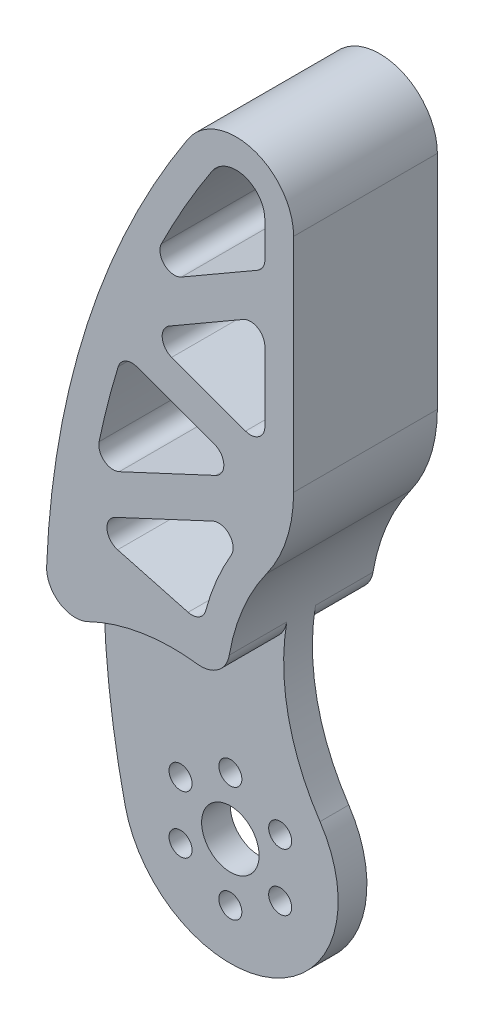
SolidWorks part; units mm, degrees
ref_plane "前视基准面" through (0, 0, 0) normal (0, 0, 1) x (1, 0, 0)
ref_plane "上视基准面" through (0, 0, 0) normal (0, 1, 0) x (1, 0, 0)
ref_plane "右视基准面" through (0, 0, 0) normal (1, 0, 0) x (0, 0, -1)
sketch "草图1" plane through (0, 0, 0) normal (0, 0, 1) x (1, 0, 0)
  circle A0 centre (0, 0) radius 4
  circle A1 centre (0, 0) radius 8 construction
  circle A2 centre (0, 0) radius 15
  circle A3 centre (0, 8) radius 1.6
  circle A4 centre (6.9282, 4) radius 1.6
  circle A5 centre (6.9282, -4) radius 1.6
  circle A6 centre (0, -8) radius 1.6
  circle A7 centre (-6.9282, -4) radius 1.6
  circle A8 centre (-6.9282, 4) radius 1.6
  point P16 (0, 0)
  dimension "D1" = 3.2
  dimension "D2" = 16
  dimension "D3" = 8
  dimension "D4" = 30
  dimension "D5" = 6
extrude "凸台-拉伸1" add sketch "草图1" along normal blind 4
sketch "草图2" plane through (0, 0, 4) normal (0, 0, 1) x (1, 0, 0)
  line L1 (16.8, 85) -> (16.8, 54.1598)
  arc A0 (-14.622, -3.3462) -> (2.1176, 89.3983) centre (102.354, 23.4236) cw
  circle A1 centre (0, 0) radius 15 construction
  arc A2 (12.4722, 8.3333) -> (13.0466, 42.4959) centre (37.4166, 25) cw
  arc A3 (12.4722, 8.3333) -> (-14.622, -3.3462) centre (0, 0) ccw
  arc A4 (2.1176, 89.3983) -> (16.8, 85) centre (8.8, 85) cw
  arc A5 (16.8, 54.1598) -> (13.0466, 42.4959) centre (-3.2, 54.1598) cw
  dimension "D1" = 8
  dimension "D4" = 30
  dimension "D5" = 120
  dimension "D6" = 20
  dimension "D2" = 85
  dimension "D3" = 16.8
  dimension "D7" = 25
extrude "凸台-拉伸3" add sketch "草图2" against normal up to surface (4 mm away) up to face at (15, 0, 0)
sketch "草图3" plane through (0, 0, 4) normal (0, 0, 1) x (1, 0, 0)
  line L1 (16.8, 54.1598) -> (16.8, 85)
  line L2 (16.8, 54.1598) -> (16.8, 85)
  arc A0 (-11.8108, 24.2797) -> (3.4027, 26.7847) centre (0, 0) cw
  arc A1 (2.1176, 89.3983) -> (-14.622, -3.3462) centre (102.354, 23.4236) ccw construction
  arc A2 (13.0466, 42.4959) -> (12.4722, 8.3333) centre (37.4166, 25) ccw construction
  circle A3 centre (0, 0) radius 4 construction
  arc A4 (3.4027, 26.7847) -> (7.8491, 30.076) centre (3.9068, 30.7528) ccw
  arc A5 (-11.8108, 24.2797) -> (-17.5576, 28.0303) centre (-13.5605, 27.8767) cw
  arc A9 (-14.622, -3.3462) -> (12.4722, 8.3333) centre (0, 0) ccw
  arc A10 (13.0466, 42.4959) -> (12.4722, 8.3333) centre (37.4166, 25) ccw
  arc A11 (13.0466, 42.4959) -> (16.8, 54.1598) centre (-3.2, 54.1598) ccw
  arc A12 (16.8, 85) -> (2.1176, 89.3983) centre (8.8, 85) ccw
  arc A13 (2.1176, 89.3983) -> (-14.622, -3.3462) centre (102.354, 23.4236) ccw
  arc A15 (13.0466, 42.4959) -> (7.8491, 30.076) centre (37.4166, 25) ccw
  arc A16 (13.0466, 42.4959) -> (16.8, 54.1598) centre (-3.2, 54.1598) ccw
  arc A17 (16.8, 85) -> (2.1176, 89.3983) centre (8.8, 85) ccw
  arc A18 (2.1176, 89.3983) -> (-17.5576, 28.0303) centre (102.354, 23.4236) ccw
  point P17 (7.4318, 25.957)
  point P27 (-17.6096, 20.4671)
  dimension "D1" = 27
  dimension "D3" = 4
  dimension "D2" = 0
extrude "凸台-拉伸4" add sketch "草图3" along normal blind 8 and the other way blind 12
sketch "草图5" plane through (0, 0, -8) normal (0, 0, -1) x (-1, 0, 0)
  line L0 (-12.8, 69.7624) -> (-12.8, 60.0828)
  line L1 (-11.8, 78.4226) -> (-1.2064, 72.3064)
  line L2 (-12.8, 85) -> (-12.8, 54.1598)
  line L3 (-12.8, 85) -> (-12.8, 80.1547)
  line L4 (-10.116, 58.2034) -> (0.167, 61.9461)
  line L5 (0.483, 65.5576) -> (-9.8, 71.4944)
  line L6 (5.0101, 58.3879) -> (-5.777, 54.4618)
  line L7 (-5.9382, 50.7698) -> (7.4531, 44.5253)
  line L8 (-2.1233, 32.3771) -> (7.682, 35.0045)
  line L9 (8.0096, 38.7489) -> (-5.5439, 45.069)
  arc A0 (7.6065, 57.0941) -> (10.2568, 46.7435) centre (-102.354, 23.4236) cw
  arc A1 (17.5576, 28.0303) -> (-2.1176, 89.3983) centre (-102.354, 23.4236) ccw construction
  arc A2 (-8.1128, 42.2421) -> (-4.5729, 33.7918) centre (-37.4166, 25) cw
  arc A3 (-7.8491, 30.076) -> (-13.0466, 42.4959) centre (-37.4166, 25) ccw construction
  arc A4 (7.682, 35.0045) -> (8.0096, 38.7489) centre (7.1643, 36.9363) ccw
  arc A5 (-5.777, 54.4618) -> (-5.9382, 50.7698) centre (-5.093, 52.5824) ccw
  arc A6 (-4.5729, 33.7918) -> (-2.1233, 32.3771) centre (-2.641, 34.309) ccw
  arc A7 (10.2568, 46.7435) -> (7.4531, 44.5253) centre (8.2983, 46.3379) cw
  arc A8 (-8.1128, 42.2421) -> (-5.5439, 45.069) centre (-6.3891, 43.2564) cw
  arc A9 (0.167, 61.9461) -> (0.483, 65.5576) centre (-0.517, 63.8255) ccw
  arc A10 (7.6065, 57.0941) -> (5.0101, 58.3879) centre (5.6941, 56.5086) ccw
  arc A11 (-12.8, 60.0828) -> (-10.116, 58.2034) centre (-10.8, 60.0828) ccw
  arc A12 (-12.8, 69.7624) -> (-9.8, 71.4944) centre (-10.8, 69.7624) cw
  arc A13 (-1.2064, 72.3064) -> (1.5857, 74.9264) centre (-0.2064, 74.0385) ccw
  arc A14 (13.5605, 27.8767) -> (-3.9068, 30.7528) centre (0, 0) ccw
  arc A15 (13.5605, 27.8767) -> (-5.4588, 87.1992) centre (-102.354, 23.4236) ccw
  arc A16 (-5.4588, 87.1992) -> (-12.8, 85) centre (-8.8, 85) ccw
  arc A17 (-12.8, 54.1598) -> (-9.7973, 44.8287) centre (3.2, 54.1598) ccw
  arc A18 (-3.9068, 30.7528) -> (-9.7973, 44.8287) centre (-37.4166, 25) ccw
  arc A20 (1.5857, 74.9264) -> (-5.4588, 87.1992) centre (-102.354, 23.4236) ccw
  arc A21 (-5.4588, 87.1992) -> (-12.8, 85) centre (-8.8, 85) ccw
  arc A22 (-11.8, 78.4226) -> (-12.8, 80.1547) centre (-10.8, 80.1547) cw
  point P39 (-4.1126, 31.8441)
  point P44 (-12.8, 48.4526)
  point P51 (-12.8, 57.2265)
  point P54 (-12.8, 73.2265)
  point P59 (-12.8, 79)
  dimension "D3" = 5
  dimension "D4" = 4
  dimension "D14" = 2
  dimension "D2" = 5
  dimension "D5" = 5
  dimension "D6" = 5
  dimension "D7" = 120
  dimension "D8" = 6
  dimension "D9" = 50
  dimension "D10" = 16
  dimension "D11" = 45
  dimension "D12" = 32
  dimension "D13" = 40
  dimension "D1" = 4
extrude "切除-拉伸1" cut sketch "草图5" against normal blind 46
